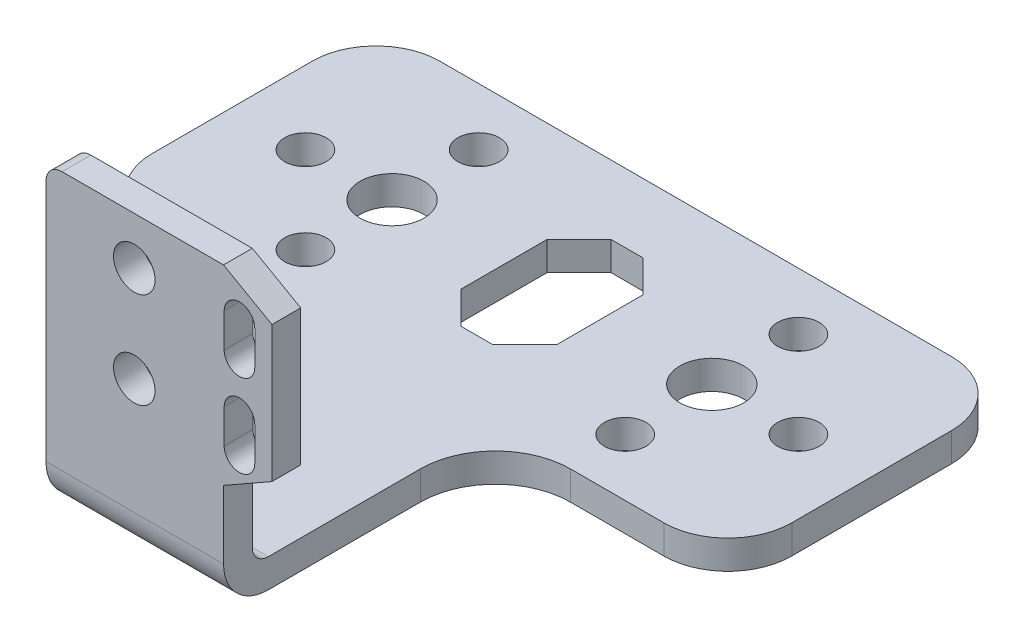
SolidWorks part; units mm, degrees
ref_plane "Front" through (0, 0, 0) normal (0, 0, 1) x (1, 0, 0)
ref_plane "Top" through (0, 0, 0) normal (0, 1, 0) x (1, 0, 0)
ref_plane "Right" through (0, 0, 0) normal (1, 0, 0) x (0, 0, -1)
sketch "Sketch1" plane through (0, 0, 0) normal (1, 0, 0) x (0, 0, -1)
  line L0 (0, 0) -> (0, 45)
  line L1 (0, 45) -> (4.5, 45)
  line L2 (4.5, 45) -> (4.5, 4.5)
  line L3 (4.5, 4.5) -> (90, 4.5)
  line L4 (90, 4.5) -> (90, 0)
  line L5 (90, 0) -> (0, 0)
  dimension "D1" = 4.5
  dimension "D2" = 4.5
  dimension "D3" = 90
  dimension "D4" = 45
extrude "Boss-Extrude1" add sketch "Sketch1" along normal mid plane 100
sketch "Sketch2" plane through (0, 0, 0) normal (0, 1, 0) x (1, 0, 0)
  line L0 (-40, 45) -> (-25.836, 45)
  line L1 (-50, 90) -> (-50, 4.5) construction
  line L2 (50, 90) -> (50, 4.5) construction
  line L4 (-14.0978, 33.2618) -> (-14.0978, 7)
  line L5 (13.6618, 33.2618) -> (13.6618, 7)
  line L7 (50, 90) -> (-50, 90) construction
  line L8 (-2.5, 79.24) -> (2.5, 79.24)
  line L9 (2.5, 79.24) -> (7.5, 74.24)
  line L10 (7.5, 74.24) -> (7.5, 60.76)
  line L11 (7.5, 60.76) -> (2.5, 55.76)
  line L12 (2.5, 55.76) -> (-2.5, 55.76)
  line L13 (-2.5, 55.76) -> (-7.5, 60.76)
  line L14 (-7.5, 60.76) -> (-7.5, 74.24)
  line L15 (-7.5, 74.24) -> (-2.5, 79.24)
  line L16 (-50, 55) -> (-50, 80)
  line L17 (-40, 90) -> (40, 90)
  line L18 (50, 80) -> (50, 55)
  line L19 (25.4, 45) -> (40, 45)
  line L20 (-14.0978, 7) -> (13.6618, 7)
  line L21 (50, 4.5) -> (-50, 4.5) construction
  circle A0 centre (-25, 67.5) radius 5
  circle A1 centre (25, 67.5) radius 5
  circle A2 centre (25, 81.04) radius 3.25
  circle A3 centre (25, 53.96) radius 3.25
  circle A4 centre (38.54, 67.5) radius 3.25
  circle A5 centre (-25, 81.04) radius 3.25
  circle A6 centre (-25, 53.96) radius 3.25
  circle A7 centre (-38.54, 67.5) radius 3.25
  arc A8 (-40, 90) -> (-50, 80) centre (-40, 80) ccw
  arc A9 (40, 90) -> (50, 80) centre (40, 80) cw
  arc A10 (-40, 45) -> (-50, 55) centre (-40, 55) cw
  arc A11 (40, 45) -> (50, 55) centre (40, 55) ccw
  arc A12 (-14.0978, 33.2618) -> (-25.836, 45) centre (-25.836, 33.2618) ccw
  arc A13 (13.6618, 33.2618) -> (25.4, 45) centre (25.4, 33.2618) cw
  point P43 (-50, 90)
  point P47 (50, 90)
  point P52 (-50, 45)
  point P55 (50, 45)
  point P60 (13.6618, 45)
  point P61 (0, 90)
  dimension "D1" = 45
  dimension "D3" = 22.5
  dimension "D14" = 6.5
  dimension "D19" = 10
  dimension "D20" = 10
  dimension "D21" = 11.7382
  dimension "D22" = 11.7382
  dimension "D2" = 22.5
  dimension "D4" = 50
  dimension "D5" = 25
  dimension "D6" = 225
  dimension "D7" = 225
  dimension "D8" = 225
  dimension "D9" = 225
  dimension "D10" = 15
  dimension "D11" = 5
  dimension "D12" = 23.48
  dimension "D13" = 17.5
  dimension "D15" = 13.54
  dimension "D16" = 13.54
  dimension "D17" = 13.54
  dimension "D18" = 13.54
  dimension "D23" = 10.76
  dimension "D24" = 2.5
  dimension "D25" = 14.164
  dimension "D26" = 14.6
  dimension "D27" = 27.7596
extrude "Cut-Extrude34" cut sketch "Sketch2" against normal through all and the other way through all flip side to cut contours L0 A12 L4 L20 L5 A13 L19 A11 L18 A9 L17 A8 L16 A10 | A6 | A0 | A5 | A7 | L10 L11 L12 L13 L14 L15 L8 L9 | A3 | A1 | A2 | A4
sketch "Sketch4" plane through (0, 0, -7) normal (0, 0, 1) x (1, 0, 0)
  line L0 (-14.0978, 0) -> (-14.0978, 45)
  line L1 (-11.5978, 47.5) -> (13.6618, 47.5)
  line L2 (13.6618, 47.5) -> (21.2228, 43.2094)
  line L3 (21.2228, 43.2094) -> (21.2228, 21.944)
  line L4 (21.2228, 21.944) -> (13.6618, 17.6534)
  line L5 (13.6618, 17.6534) -> (13.6618, 4.5)
  line L6 (13.6618, 4.5) -> (13.6618, 0)
  line L7 (13.6618, 0) -> (-14.0978, 0)
  arc A0 (-11.5978, 47.5) -> (-14.0978, 45) centre (-11.5978, 45) ccw
  dimension "D1" = 2.5
  dimension "D2" = 45
extrude "Boss-Extrude3" add sketch "Sketch4" along normal blind 4.5 contours L0 A0 L1 L2 L3 L4 L5 L6 L7
fillet "Fillet3" radius 2.5 1 edges at (-0.218, 4.5, -7)
fillet "Fillet4" radius 7 1 edges at (-0.218, 0, -2.5)
sketch "Sketch6" plane through (0, 0, -2.5) normal (0, 0, 1) x (1, 0, 0)
  line L1 (-14.0978, 7) -> (-14.0978, 45) construction
  circle A0 centre (-0.2978, 40.0831) radius 3.25
  circle A1 centre (-0.2978, 25.0831) radius 3.25
  dimension "D1" = 6.5
  dimension "D2" = 6.5
  dimension "D3" = 15
  dimension "D4" = 13.8
sketch "Sketch7" plane through (0, 0, -2.5) normal (0, 0, 1) x (1, 0, 0)
  line L0 (16.1496, 41.3556) -> (16.1496, 36.0322) construction
  line L1 (18.5396, 41.3556) -> (18.5396, 36.0322)
  line L2 (13.7596, 41.3556) -> (13.7596, 36.0322)
  line L3 (16.1496, 28.3556) -> (16.1496, 23.0322) construction
  line L4 (18.5396, 28.3556) -> (18.5396, 23.0322)
  line L5 (13.7596, 28.3556) -> (13.7596, 23.0322)
  arc A0 (18.5396, 41.3556) -> (13.7596, 41.3556) centre (16.1496, 41.3556) ccw
  arc A1 (13.7596, 36.0322) -> (18.5396, 36.0322) centre (16.1496, 36.0322) ccw
  arc A2 (18.5396, 28.3556) -> (13.7596, 28.3556) centre (16.1496, 28.3556) ccw
  arc A3 (13.7596, 23.0322) -> (18.5396, 23.0322) centre (16.1496, 23.0322) ccw
  point P2 (16.1496, 38.6939)
  point P7 (16.1496, 25.6939)
  dimension "D1" = 4.78
  dimension "D2" = 4.78
  dimension "D3" = 13
extrude "Cut-Extrude35" cut sketch "Sketch6" against normal through all both and the other way through all
extrude "Cut-Extrude39" cut sketch "Sketch7" against normal blind 5.18
